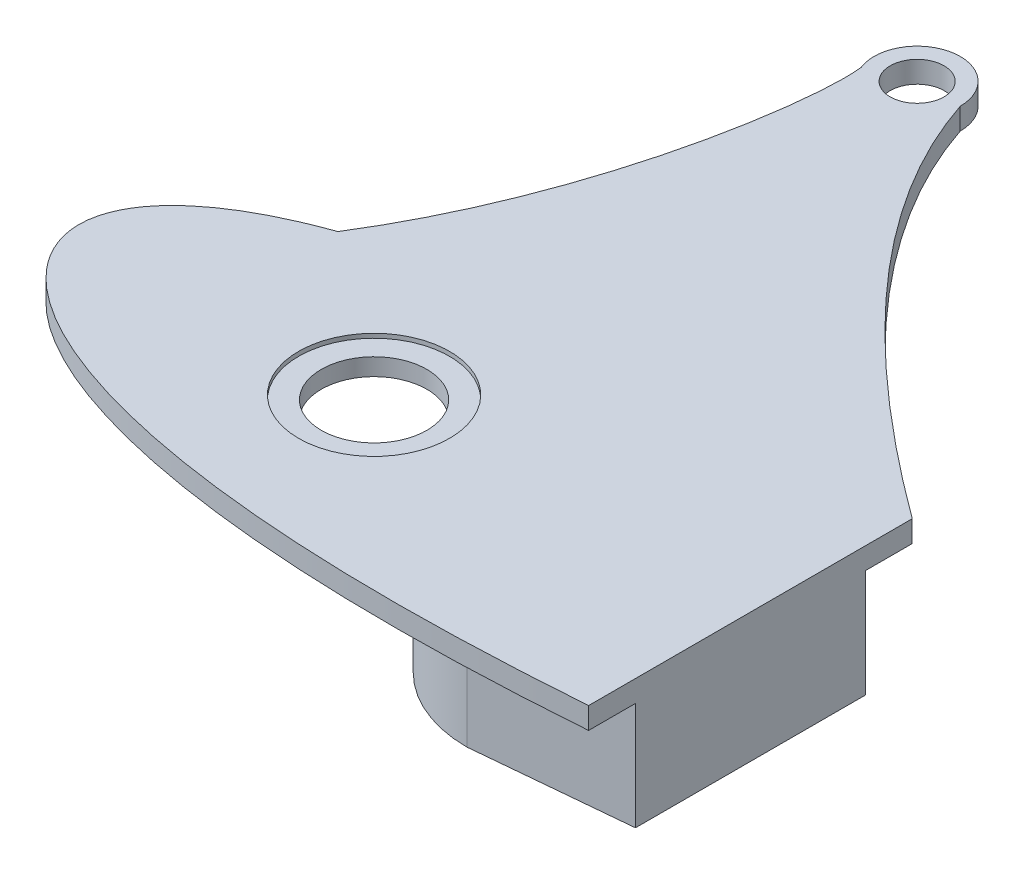
SolidWorks part; units mm, degrees
material "ABS"
ref_plane "Front Plane" through (0, 0, 0) normal (0, 0, 1) x (1, 0, 0)
ref_plane "Top Plane" through (0, 0, 0) normal (0, 1, 0) x (1, 0, 0)
ref_plane "Right Plane" through (0, 0, 0) normal (1, 0, 0) x (0, 0, -1)
sketch "Sketch1" plane through (0, 0, 0) normal (0, 1, 0) x (1, 0, 0)
  line L0 (-71.828, 0) -> (-71.828, -6.223) construction
  line L8 (-66.748, 63.9943) -> (-59.6628, 42.6773) construction
  line L9 (-59.6628, 42.6773) -> (-27.4798, 19.0692) construction
  line L10 (-97.2956, 0) -> (-106.6082, 0)
  line L11 (-45.666, 15.24) -> (-27.4798, 13.5444)
  line L12 (-45.666, -15.24) -> (-27.4798, -13.5444)
  line L13 (-27.4798, 19.0692) -> (-27.4798, -19.0692)
  line L14 (-90.6222, 14.5334) -> (-78.6766, 33.624) construction
  line L15 (-78.6766, 33.624) -> (-75.814, 56.6964) construction
  line L16 (-75.814, 56.6964) -> (-76.5562, 62.1367) construction
  arc A5 (-42.8488, 14.9773) -> (-42.8488, -14.9773) centre (-45.666, 0) ccw
  circle A6 centre (-71.828, 0) radius 6.223
  circle A7 centre (-93.0623, 0) radius 4.2333
  arc A11 (-76.5562, 62.1367) -> (-66.748, 63.9943) centre (-71.828, 63.9943) cw
  circle A12 centre (-71.828, 63.9943) radius 3.175
  spline S0 degree 3 poles (-106.6082, 0) (-106.6072, -0.3362) (-106.5531, -1.1725) (-106.2311, -2.6431) (-105.4392, -4.4752) (-104.0227, -6.5043) (-101.9332, -8.5717) (-99.1919, -10.5676) (-95.845, -12.4267) (-91.9425, -14.1114) (-87.5319, -15.5993) (-82.6571, -16.8771) (-77.3593, -17.9374) (-71.6778, -18.7767) (-65.6503, -19.3955) (-59.3138, -19.7966) (-52.7042, -19.9863) (-45.8572, -19.9729) (-38.8076, -19.7673) (-32.6592, -19.4396) (-28.8658, -19.174) (-27.4798, -19.0692) knots 0.5 0.5 0.5 0.5 0.502167 0.50539 0.509656 0.514948 0.521245 0.528521 0.536745 0.545881 0.555891 0.56673 0.578353 0.59071 0.603747 0.61741 0.631639 0.646374 0.661552 0.677107 0.68607 0.68607 0.68607 0.68607
  spline S1 degree 3 poles (-106.6082, 0) (-106.6072, 0.3362) (-106.5531, 1.1725) (-106.2311, 2.6431) (-105.4392, 4.4752) (-104.0227, 6.5043) (-101.9332, 8.5717) (-99.1919, 10.5676) (-95.845, 12.4267) (-92.9041, 13.6963) (-91.0996, 14.3638) (-90.6222, 14.5334) knots 0.5 0.5 0.5 0.5 0.502167 0.50539 0.509656 0.514948 0.521245 0.528521 0.536745 0.545881 0.549147 0.549147 0.549147 0.549147
  spline S4 degree 2 poles (-66.748, 63.9943) (-59.6628, 42.6773) (-27.4798, 19.0692) knots 0 0 0 1 1 1
  spline S5 degree 3 poles (-90.6222, 14.5334) (-78.6766, 33.624) (-75.814, 56.6964) (-76.5562, 62.1367) knots 0 0 0 0 1 1 1 1
  dimension "D1" = 6.35
  dimension "D2" = 30.48
  dimension "D4" = 12.446
  dimension "D5" = 26.162
extrude "Boss-Extrude1" add sketch "Sketch1" along normal blind 2.54 contours A6 | S0 | S0 L13 S4 A11 S5 S1 | A12 region at (-71.828, 0, 0)
extrude "Boss-Extrude2" add sketch "Sketch1<3>" against normal blind 12.7 contours L11 A5 L12 L13 | A7 region at (-43.0691, 0, 0)
sketch "Sketch1<3>" plane through (0, 0, 0) normal (0, 1, 0) x (1, 0, 0) same geometry as "Sketch1"
sketch "Sketch2" plane through (0, 2.54, 0) normal (0, 1, 0) x (1, 0, 0)
  line L2 (-27.4798, -19.0692) -> (-27.4798, 19.0692)
  arc A2 (-75.9894, -62.1367) -> (-66.1812, -63.9943) centre (-71.2612, -63.9943) ccw
  circle A4 centre (-71.828, 0) radius 8.89
  parabola Q2 (-66.1812, -63.9943) -> (-27.4798, -19.0692) focus (-51.2168, -76.1585) apex (-67.7054, -77.6304)
  spline S6 degree 3 poles (-27.4798, 19.0692) (-28.8658, 19.174) (-32.6592, 19.4396) (-38.8076, 19.7673) (-45.8572, 19.9729) (-52.7042, 19.9863) (-59.3138, 19.7966) (-65.6503, 19.3955) (-71.6778, 18.7767) (-77.3593, 17.9374) (-82.6571, 16.8771) (-87.5319, 15.5993) (-91.9425, 14.1114) (-95.845, 12.4267) (-99.1919, 10.5676) (-101.9332, 8.5717) (-104.0227, 6.5043) (-105.4392, 4.4752) (-106.2311, 2.6431) (-106.5531, 1.1725) (-106.6072, 0.3362) (-106.6082, 0) knots 0.5 0.5 0.5 0.5 0.508962 0.524518 0.539696 0.554431 0.56866 0.582323 0.59536 0.607717 0.61934 0.630179 0.640188 0.649325 0.657549 0.664825 0.671122 0.676414 0.68068 0.683903 0.68607 0.68607 0.68607 0.68607
  spline S7 degree 3 poles (-106.6082, 0) (-106.6072, -0.3362) (-106.5531, -1.1725) (-106.2311, -2.6431) (-105.4392, -4.4752) (-104.0227, -6.5043) (-101.9332, -8.5717) (-99.1919, -10.5676) (-95.845, -12.4267) (-92.9041, -13.6963) (-91.0996, -14.3638) (-90.6222, -14.5334) knots 0.5 0.5 0.5 0.5 0.502167 0.50539 0.509656 0.514948 0.521245 0.528521 0.536745 0.545881 0.549147 0.549147 0.549147 0.549147
  spline S8 degree 3 poles (-90.6222, -14.5334) (-78.6766, -33.624) (-75.814, -56.6964) (-75.9894, -62.1367) knots 0 0 0 0 1 1 1 1
  circle M29 centre (-71.828, 0) radius 6.223
  dimension "D2" = 17.78
extrude "Cut-Extrude2" cut sketch "Sketch2" against normal blind 0.508 contours A4 M29 | A4 region at (-80.4666, 2.54, 0)
